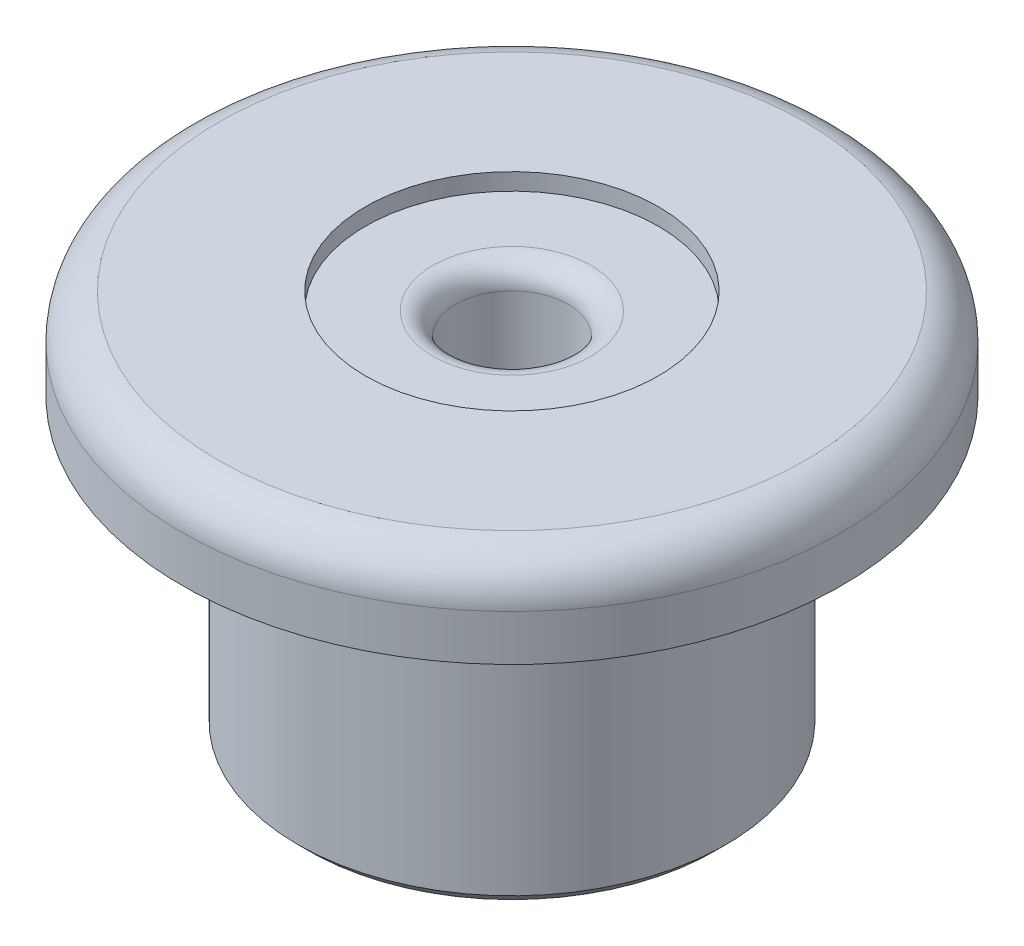
SolidWorks part; units mm, degrees
ref_plane "Front Plane" through (0, 0, 0) normal (0, 0, 1) x (1, 0, 0)
ref_plane "Top Plane" through (0, 0, 0) normal (0, 1, 0) x (1, 0, 0)
ref_plane "Right Plane" through (0, 0, 0) normal (1, 0, 0) x (0, 0, -1)
sketch "Sketch1" plane through (0, 0, 0) normal (0, 0, 1) x (1, 0, 0)
  line L0 (0, 0) -> (0, 20.778) construction
  line L1 (0, 17) -> (0, 10.2867)
  line L2 (0, 17) -> (13, 17)
  line L3 (14.616, 15.0372) -> (14.616, 13)
  line L4 (14.616, 13) -> (9.5, 13)
  line L5 (9.5, 13) -> (9.5, 0)
  line L6 (7.5762, 1.4) -> (7.5762, 0)
  line L7 (9.5, 0) -> (7.5762, 0)
  arc A0 (13, 17) -> (14.616, 15.0372) centre (12.616, 15.0372) cw
  arc A1 (0, 10.2867) -> (7.5762, 1.4) centre (-1.4238, 1.4) cw
  point P8 (0, 0)
  dimension "D3" = 2
  dimension "D7" = 9
  dimension "D1" = 17
  dimension "D2" = 26
  dimension "D4" = 4
  dimension "D5" = 19
  dimension "D6" = 1.4
revolve "Revolve1" add sketch "Sketch1" angle 360 about L0
sketch "Sketch2" plane through (0, 17, 0) normal (0, 1, 0) x (1, 0, 0)
  circle A0 centre (0, 0) radius 6.5
  dimension "D1" = 13
extrude "Cut-Extrude1" cut sketch "Sketch2" against normal blind 0.75
sketch "Sketch3" plane through (0, 16.25, 0) normal (0, 1, 0) x (1, 0, 0)
  circle A0 centre (0, 0) radius 2.5
  dimension "D1" = 5
extrude "Cut-Extrude2" cut sketch "Sketch3" against normal blind 65.75
ref_plane "Plane1" through (0, 17, 0) normal (0, 1, 0) x (1, 0, 0)
ref_plane "Plane2" through (0, -8, 0) normal (0, 1, 0) x (1, 0, 0)
sketch "Sketch5" plane through (0, -8, 0) normal (0, 1, 0) x (1, 0, 0)
  circle A0 centre (0, 0) radius 3
  dimension "D1" = 6
extrude "Cut-Extrude6" cut sketch "Sketch5" along normal blind 19 contours A0
chamfer "Chamfer1" distance 0.5 angle 45 1 edges at (0, 0, -9.5)
fillet "Fillet1" radius 1 2 edges at (0, 16.25, 2.5) (0, 11, 3)
